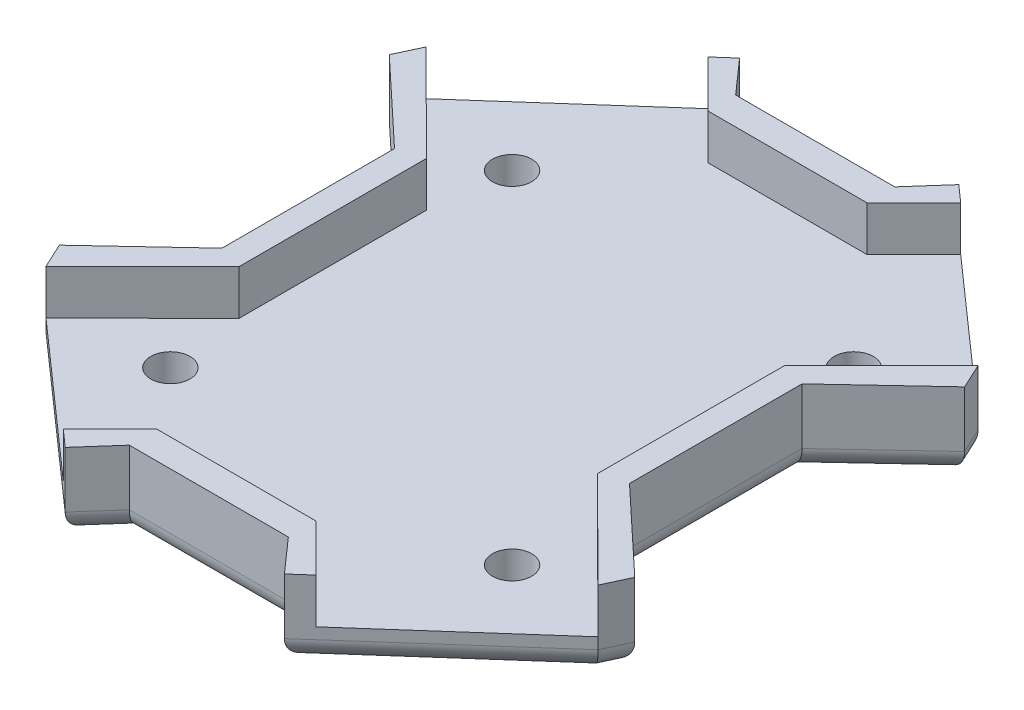
SolidWorks part; units mm, degrees
ref_plane "Front Plane" through (0, 0, 0) normal (0, 0, 1) x (1, 0, 0)
ref_plane "Top Plane" through (0, 0, 0) normal (0, 1, 0) x (1, 0, 0)
ref_plane "Right Plane" through (0, 0, 0) normal (1, 0, 0) x (0, 0, -1)
sketch "Sketch1" plane through (0, 0, 0) normal (0, 1, 0) x (1, 0, 0)
  line L1 (27.5, -32.215) -> (-27.5, -32.215)
  line L2 (27.5, -32.215) -> (27.5, 32.215)
  line L3 (27.5, 32.215) -> (-27.5, 32.215)
  line L4 (-27.5, -32.215) -> (-27.5, 32.215)
  line L5 (27.5, -32.215) -> (-27.5, 32.215) construction
  line L6 (27.5, 32.215) -> (-27.5, -32.215) construction
  point P0 (0, 0)
  dimension "D1" = 64.43
  dimension "D2" = 55
extrude "Boss-Extrude1" add sketch "Sketch1" along normal blind 3
sketch "Sketch2" plane through (0, 3, 0) normal (0, 1, 0) x (1, 0, 0)
  line L0 (-27.5, -32.215) -> (-27.5, 0) construction
  line L1 (-27.5, 32.215) -> (-27.5, -32.215) construction
  line L2 (-27.5, -32.215) -> (0, -32.215) construction
  line L3 (-27.5, -32.215) -> (27.5, -32.215) construction
  line L4 (-27.5, -4.7913) -> (-27.5, -14.3738)
  line L5 (-27.5, 0) -> (-17.5, 0) construction
  line L6 (-27.5, 4.7913) -> (-27.5, -4.7913)
  line L8 (-17.5, 5) -> (-17.5, -5)
  line L9 (-27.5, -14.3738) -> (-17.5, -5)
  line L10 (0, -32.215) -> (0, 32.215) construction
  line L11 (27.5, 32.215) -> (-27.5, 32.215) construction
  line L12 (-27.5, 14.3738) -> (-17.5, 5)
  line L13 (-27.5, 4.7913) -> (-27.5, 14.3738)
  line L14 (27.5, 4.7913) -> (27.5, 14.3738)
  line L15 (27.5, 14.3738) -> (17.5, 5)
  line L16 (27.5, 4.7913) -> (27.5, -4.7913)
  line L17 (27.5, 0) -> (17.5, 0) construction
  line L18 (17.5, 5) -> (17.5, -5)
  line L19 (27.5, -14.3738) -> (17.5, -5)
  line L20 (27.5, -4.7913) -> (27.5, -14.3738)
  dimension "D1" = 10
  dimension "D2" = 5
extrude "Cut-Extrude1" cut sketch "Sketch2" against normal blind 4
sketch "Sketch3" plane through (0, 3, 0) normal (0, 1, 0) x (1, 0, 0)
  line L0 (-27.5, 14.3738) -> (27.5, 14.3738) construction
  line L1 (0, -32.215) -> (0, 32.215) construction
  line L2 (-27.5, -32.215) -> (27.5, -32.215) construction
  line L3 (27.5, 32.215) -> (-27.5, 32.215) construction
  line L4 (-17.5, 0) -> (17.5, 0) construction
  line L5 (-17.5, -5) -> (-17.5, 5) construction
  line L6 (17.5, 5) -> (17.5, -5) construction
  line L7 (-27.5, 14.3738) -> (-25.8679, 17.8738)
  line L8 (-17.5, 5) -> (-17.5, 0)
  line L9 (-25.8679, 17.8738) -> (27.5, 17.8738) construction
  line L10 (27.5, 14.3738) -> (27.5, 32.215) construction
  line L11 (-25.8679, 17.8738) -> (-25.8679, 32.215) construction
  line L12 (-25.8679, 17.8738) -> (-9.6529, 32.215)
  line L13 (-9.6529, 32.215) -> (-3.7424, 25.5322)
  line L14 (-3.7424, 25.5322) -> (3.7424, 25.5322)
  line L15 (9.6529, 32.215) -> (3.7424, 25.5322)
  line L16 (25.8679, 17.8738) -> (9.6529, 32.215)
  line L17 (27.5, 14.3738) -> (25.8679, 17.8738)
  line L27 (-17.5, 5) -> (-27.5, 14.3738)
  line L30 (17.5, 5) -> (27.5, 14.3738)
  line L31 (17.5, 5) -> (17.5, -5)
  line L32 (17.5, -5) -> (27.5, -14.3738)
  line L33 (27.5, -14.3738) -> (25.8679, -17.8738)
  line L34 (25.8679, -17.8738) -> (9.6529, -32.215)
  line L35 (9.6529, -32.215) -> (3.7424, -25.5322)
  line L36 (-3.7424, -25.5322) -> (3.7424, -25.5322)
  line L37 (-9.6529, -32.215) -> (-3.7424, -25.5322)
  line L38 (-25.8679, -17.8738) -> (-9.6529, -32.215)
  line L39 (-27.5, -14.3738) -> (-25.8679, -17.8738)
  line L40 (-17.5, -5) -> (-27.5, -14.3738)
  line L41 (-17.5, -5) -> (-17.5, 0)
  line L42 (-16, -5.6499) -> (-16, 0)
  line L43 (-16, 5.6499) -> (-16, 0)
  line L44 (-16, 5.6499) -> (-25.6812, 14.7249)
  line L45 (-25.6812, 14.7249) -> (-24.6404, 16.957)
  line L46 (-24.6404, 16.957) -> (-9.7828, 30.0977)
  line L47 (-9.7828, 30.0977) -> (-4.4183, 24.0322)
  line L48 (-4.4183, 24.0322) -> (4.4183, 24.0322)
  line L49 (9.7828, 30.0977) -> (4.4183, 24.0322)
  line L50 (24.6404, 16.957) -> (9.7828, 30.0977)
  line L51 (25.6812, 14.7249) -> (24.6404, 16.957)
  line L52 (16, 5.6499) -> (25.6812, 14.7249)
  line L53 (16, 5.6499) -> (16, -5.6499)
  line L54 (16, -5.6499) -> (25.6812, -14.7249)
  line L55 (25.6812, -14.7249) -> (24.6404, -16.957)
  line L56 (24.6404, -16.957) -> (9.7828, -30.0977)
  line L57 (9.7828, -30.0977) -> (4.4183, -24.0322)
  line L58 (-4.4183, -24.0322) -> (4.4183, -24.0322)
  line L59 (-9.7828, -30.0977) -> (-4.4183, -24.0322)
  line L60 (-24.6404, -16.957) -> (-9.7828, -30.0977)
  line L61 (-25.6812, -14.7249) -> (-24.6404, -16.957)
  line L62 (-16, -5.6499) -> (-25.6812, -14.7249)
  point P27 (0, 23.6915)
  dimension "D1" = 1.5
  dimension "D2" = 3.5
extrude "Cut-Extrude4" cut sketch "Sketch3" against normal blind 4 flip side to cut contours L42 L43 L44 L45 L46 L47 L48 L49 L50 L51 L52 L53 L54 L55 L56 L57 L58 L59 L60 L61 L62
sketch "Sketch4" plane through (0, 3, 0) normal (0, 1, 0) x (1, 0, 0)
  line L0 (-7.1005, 27.0649) -> (7.1005, 27.0649)
  line L1 (-9.7828, 30.0977) -> (-4.4183, 24.0322) construction
  line L2 (9.7828, 30.0977) -> (4.4183, 24.0322) construction
  line L3 (-7.1005, -27.0649) -> (7.1005, -27.0649)
  line L4 (-9.7828, -30.0977) -> (-4.4183, -24.0322) construction
  line L5 (9.7828, -30.0977) -> (4.4183, -24.0322) construction
  line L6 (7.1005, -27.0649) -> (4.4183, -24.0322)
  line L7 (4.4183, -24.0322) -> (-4.4183, -24.0322)
  line L8 (-4.4183, -24.0322) -> (-7.1005, -27.0649)
  line L9 (-7.1005, 27.0649) -> (-4.4183, 24.0322)
  line L10 (-4.4183, 24.0322) -> (4.4183, 24.0322)
  line L11 (4.4183, 24.0322) -> (7.1005, 27.0649)
extrude "Boss-Extrude2" add sketch "Sketch4" against normal blind 3
sketch "Sketch5" plane through (0, 3, 0) normal (0, 1, 0) x (1, 0, 0)
  line L0 (-16, 5.6499) -> (-18.1887, 7.7016)
  line L1 (-16, 5.6499) -> (-25.6812, 14.7249) construction
  line L2 (-16, -5.6499) -> (-18.1887, -7.7016)
  line L3 (-16, -5.6499) -> (-25.6812, -14.7249) construction
  line L4 (-18.1887, 7.7016) -> (-18.1887, -7.7016)
  line L5 (-16, 5.6499) -> (-16, -5.6499)
  line L6 (0, 27.0649) -> (0, -27.0649) construction
  line L7 (7.1005, 27.0649) -> (-7.1005, 27.0649) construction
  line L8 (-7.1005, -27.0649) -> (7.1005, -27.0649) construction
  line L9 (16, 5.6499) -> (18.1887, 7.7016)
  line L10 (18.1887, 7.7016) -> (18.1887, -7.7016)
  line L11 (16, -5.6499) -> (18.1887, -7.7016)
  line L12 (16, 5.6499) -> (16, -5.6499)
  dimension "D1" = 3
  dimension "D2" = 3
extrude "Boss-Extrude3" add sketch "Sketch5" against normal blind 3
sketch "Sketch6" plane through (0, 3, 0) normal (0, 1, 0) x (1, 0, 0)
  line L0 (-24.6404, -16.957) -> (-25.6812, -14.7249)
  line L1 (-25.6812, -14.7249) -> (-18.1887, -7.7016)
  line L2 (-18.1887, -7.7016) -> (-18.1887, 7.7016)
  line L3 (-18.1887, 7.7016) -> (-25.6812, 14.7249)
  line L4 (-25.6812, 14.7249) -> (-24.6404, 16.957)
  line L5 (-24.6404, 16.957) -> (-16, 8.3734)
  line L6 (-16, 8.3734) -> (-16, -8.3734)
  line L7 (-16, -8.3734) -> (-24.6404, -16.957)
  line L8 (-18.1887, 7.7016) -> (-18.1887, -7.7016) construction
  line L9 (0, 27.0649) -> (0, -27.0649) construction
  line L10 (7.1005, 27.0649) -> (-7.1005, 27.0649) construction
  line L11 (-7.1005, -27.0649) -> (7.1005, -27.0649) construction
  line L12 (16, -8.3734) -> (24.6404, -16.957)
  line L13 (16, 8.3734) -> (16, -8.3734)
  line L14 (24.6404, 16.957) -> (16, 8.3734)
  line L15 (25.6812, 14.7249) -> (24.6404, 16.957)
  line L16 (18.1887, 7.7016) -> (25.6812, 14.7249)
  line L17 (18.1887, -7.7016) -> (18.1887, 7.7016)
  line L18 (25.6812, -14.7249) -> (18.1887, -7.7016)
  line L19 (24.6404, -16.957) -> (25.6812, -14.7249)
extrude "Boss-Extrude4" add sketch "Sketch6" along normal blind 4
sketch "Sketch7" plane through (0, 3, 0) normal (0, 1, 0) x (1, 0, 0)
  line L1 (-1, 27.0649) -> (-7.1005, 27.0649)
  line L2 (-7.1005, 27.0649) -> (-9.7828, 30.0977)
  line L3 (-9.7828, 30.0977) -> (-11.2809, 28.7727)
  line L4 (-1, 24.5949) -> (-7.1005, 24.5949)
  line L5 (-7.1005, 24.5949) -> (-11.2809, 28.7727)
  line L6 (0, 27.0649) -> (0, -27.0649) construction
  line L7 (7.1005, 27.0649) -> (-7.1005, 27.0649) construction
  line L8 (-7.1005, -27.0649) -> (7.1005, -27.0649) construction
  line L9 (-1, 27.0649) -> (1, 27.0649)
  line L10 (-1, 24.5949) -> (1, 24.5949)
  line L12 (1, 24.5949) -> (7.1005, 24.5949)
  line L13 (7.1005, 24.5949) -> (11.2809, 28.7727)
  line L14 (9.7828, 30.0977) -> (11.2809, 28.7727)
  line L15 (7.1005, 27.0649) -> (9.7828, 30.0977)
  line L16 (1, 27.0649) -> (7.1005, 27.0649)
  line L17 (-18.1887, 0) -> (18.1887, 0) construction
  line L18 (-18.1887, 7.7016) -> (-18.1887, -7.7016) construction
  line L19 (18.1887, -7.7016) -> (18.1887, 7.7016) construction
  line L20 (-1, -27.0649) -> (-7.1005, -27.0649)
  line L21 (-7.1005, -27.0649) -> (-9.7828, -30.0977)
  line L22 (-9.7828, -30.0977) -> (-11.2809, -28.7727)
  line L23 (-7.1005, -24.5949) -> (-11.2809, -28.7727)
  line L24 (-1, -24.5949) -> (-7.1005, -24.5949)
  line L25 (-1, -24.5949) -> (1, -24.5949)
  line L26 (1, -24.5949) -> (7.1005, -24.5949)
  line L27 (7.1005, -24.5949) -> (11.2809, -28.7727)
  line L28 (9.7828, -30.0977) -> (11.2809, -28.7727)
  line L29 (7.1005, -27.0649) -> (9.7828, -30.0977)
  line L30 (1, -27.0649) -> (7.1005, -27.0649)
  line L31 (-1, -27.0649) -> (1, -27.0649)
extrude "Boss-Extrude5" add sketch "Sketch7" along normal blind 4 contours L9 L16 L15 L14 L13 L12 L10 L4 L5 L3 L2 L1 | L20 L21 L22 L23 L24 L25 L26 L27 L28 L29 L30 L31
fillet "Fillet1" radius 2 20 edges at (25.1608, 0, -15.841) (21.935, 0, -11.2133) (18.1887, 0, 0) (21.935, 0, 11.2133) (25.1608, 0, 15.841) (17.2116, 0, 23.5273) (8.4416, 0, 28.5813) (0, 0, 27.0649) (-8.4416, 0, 28.5813) (-17.2116, 0, 23.5273) (-25.1608, 0, 15.841) (-21.935, 0, 11.2133) (-18.1887, 0, 0) (-25.1608, 0, -15.841) (-21.935, 0, -11.2133) (-17.2116, 0, -23.5273) (-8.4416, 0, -28.5813) (0, 0, -27.0649) (8.4416, 0, -28.5813) (17.2116, 0, -23.5273)
sketch "Sketch9" plane through (0, 3, 0) normal (0, 1, 0) x (1, 0, 0)
  line L0 (25.6812, -14.7249) -> (24.6404, -16.957) construction
  line L1 (25.6812, -14.7249) -> (15.2512, -15.2442) construction
  line L3 (15.2512, -15.2442) -> (-15.2488, -15.2442) construction
  line L4 (15.2512, -15.2442) -> (15.2512, 15.2558) construction
  line L5 (15.2512, 15.2558) -> (-15.2488, 15.2558) construction
  line L6 (-15.2488, -15.2442) -> (-15.2488, 15.2558) construction
  circle A0 centre (15.2512, -15.2442) radius 1.75
  circle A1 centre (15.2512, 15.2558) radius 1.75
  circle A2 centre (-15.2488, 15.2558) radius 1.75
  circle A3 centre (-15.2488, -15.2442) radius 1.75
  dimension "D5" = 3.5
  dimension "D6" = 3.5
  dimension "D7" = 3.5
  dimension "D8" = 3.5
  dimension "D1" = 62.15
  dimension "D2" = 10.43
  dimension "D3" = 30.5
  dimension "D4" = 30.5
extrude "Cut-Extrude6" cut sketch "Sketch9" against normal through all
